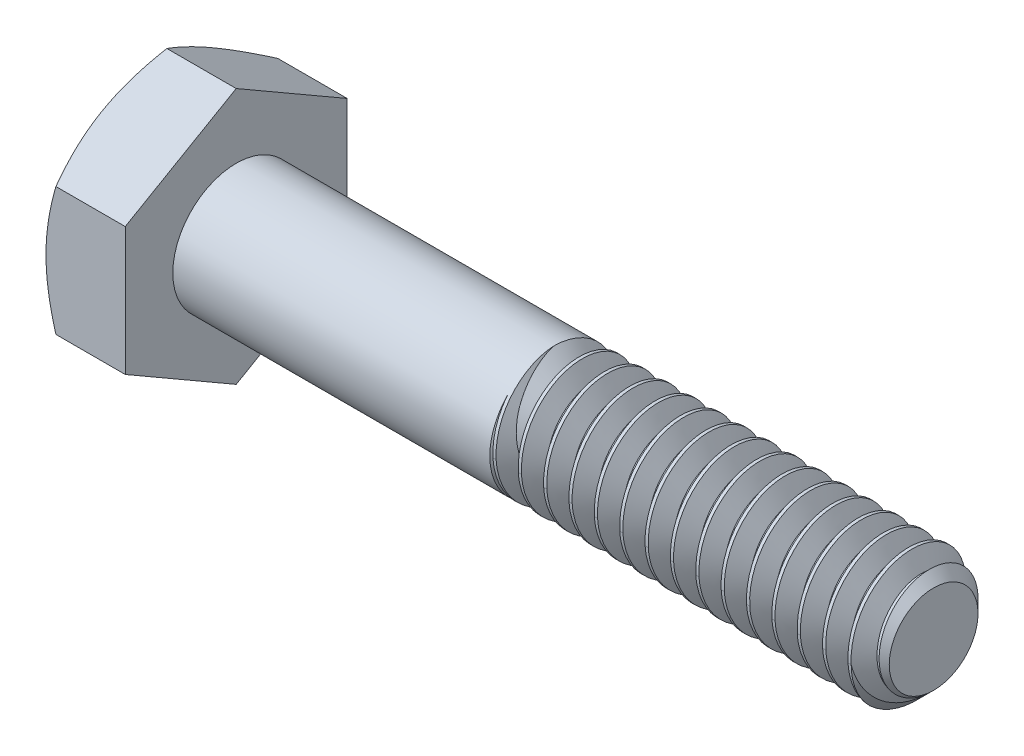
SolidWorks part; units mm, degrees
ref_plane "Front Plane" through (0, 0, 0) normal (0, 0, 1) x (1, 0, 0)
ref_plane "Top Plane" through (0, 0, 0) normal (0, 1, 0) x (1, 0, 0)
ref_plane "Right Plane" through (0, 0, 0) normal (1, 0, 0) x (0, 0, -1)
sketch "Sketch1" plane through (0, 0, 0) normal (0, 0, 1) x (1, 0, 0)
  line L0 (-19.4469, 0) -> (19.4469, 0) construction
  line L1 (19.4469, 3.175) -> (19.4469, -3.175) construction
  line L2 (-15.4781, 5.5562) -> (-15.4781, -5.5562) construction
  line L3 (-19.4469, 5.5562) -> (-19.4469, -5.5562) construction
  point P9 (-15.4781, 0)
  point P10 (15.0019, -3.175)
  dimension "Screw Dia" = 6.35
  dimension "Hex" = 11.1125
  dimension "Head Ht" = 3.9688
  dimension "Screw Lenght" = 34.925
  dimension "D1" = 4.445
ref_plane "Plane2" through (19.4469, 0, 0) normal (1, 0, 0) x (0, 0, -1)
sketch "Sketch5" plane through (19.4469, 0, 0) normal (1, 0, 0) x (0, 0, -1)
  circle A0 centre (0, 0) radius 3.175
extrude "Boss-Extrude3" add sketch "Sketch5" against normal up to vertex (34.925 mm away) up to point (-15.4781, 0, 0)
sketch "Sketch9" plane through (19.4469, 0, 0) normal (1, 0, 0) x (0, 0, -1)
  circle A1 centre (0, 0) radius 3.175
  circle A2 centre (0, 0) radius 3.175
  dimension "D1" = 0
curve "Helix/Spiral1" pitch 1.27 height 20.32 turns 16 parameters "Pitch"=1.27
chamfer "Chamfer1" distance 0.9525 angle 45 1 edges at (19.4469, 0, -3.175)
sketch "Sketch10" plane through (0, 0, 0) normal (0, 0, 1) x (1, 0, 0)
  line L0 (19.4469, 3.175) -> (19.9231, 2.3501)
  line L1 (19.9231, 2.3501) -> (20.0819, 2.3501)
  line L2 (20.0819, 2.3501) -> (20.5581, 3.175)
  line L3 (19.4469, 3.175) -> (20.5581, 3.175)
  line L4 (20.0025, 3.175) -> (20.0025, 2.3501) construction
  line L5 (19.685, 2.7626) -> (20.32, 2.7626) construction
  dimension "D1" = 60
  dimension "D2" = 0.1588
  dimension "D3" = 0.635
sweep "Cut-Sweep1" cut profiles "Sketch10" path "Helix/Spiral1" align with end faces yes
sketch "Sketch11" plane through (0, 0, 0) normal (0, 0, 1) x (1, 0, 0)
  line L0 (-15.4781, 3.175) -> (-15.4781, 0)
  line L1 (-15.4781, 0) -> (3.5719, 0)
  line L3 (3.5719, 0) -> (0.3969, 3.175)
  line L4 (-15.4781, 3.175) -> (0.3969, 3.175)
  dimension "D1" = 45
  dimension "MIn Thread" = 19.05
revolve "Revolve1" add sketch "Sketch11" angle 360 about L1
sketch "Sketch6" plane through (-15.4781, 0, 0) normal (-1, 0, 0) x (0, 0, 1)
  line L0 (0, 5.5562) -> (0, -5.5562) construction
  line L1 (5.5562, 3.2079) -> (0, 6.4158)
  line L2 (0, 6.4158) -> (-5.5562, 3.2079)
  line L3 (-5.5562, 3.2079) -> (-5.5562, -3.2079)
  line L4 (-5.5562, -3.2079) -> (0, -6.4158)
  line L5 (0, -6.4158) -> (5.5562, -3.2079)
  line L6 (5.5562, -3.2079) -> (5.5562, 3.2079)
  circle A0 centre (0, 0) radius 5.5562 construction
extrude "Boss-Extrude4" add sketch "Sketch6" along normal up to vertex (3.9688 mm away) up to point (-19.4469, -5.5562, 0)
sketch "Sketch7" plane through (-19.4469, 0, 0) normal (-1, 0, 0) x (0, 0, 1)
  circle A0 centre (0, 0) radius 5.5562 construction
  circle A1 centre (0, 0) radius 5.5562
sketch "Sketch8" plane through (-19.4469, 0, 0) normal (-1, 0, 0) x (0, 0, 1)
  circle A0 centre (0, 0) radius 5.5562 construction
  circle A1 centre (0, 0) radius 5.5562
extrude "Cut-Extrude3" cut sketch "Sketch8" against normal through all draft 60 flip side to cut
equation "\"D2@Sketch10\" = \"Pitch@Helix/Spiral1\"*.125"
equation "\"D3@Sketch10\" = \"Pitch@Helix/Spiral1\"*.5"
equation "\"D3@Helix/Spiral1\" = \"MIn Thread@Sketch11\"+\"Pitch@Helix/Spiral1\""
equation "\"D1@Chamfer1\" = \"Pitch@Helix/Spiral1\"*.75"
equation "\"D1@Sketch1\" = \"Pitch@Helix/Spiral1\"*3.5"
